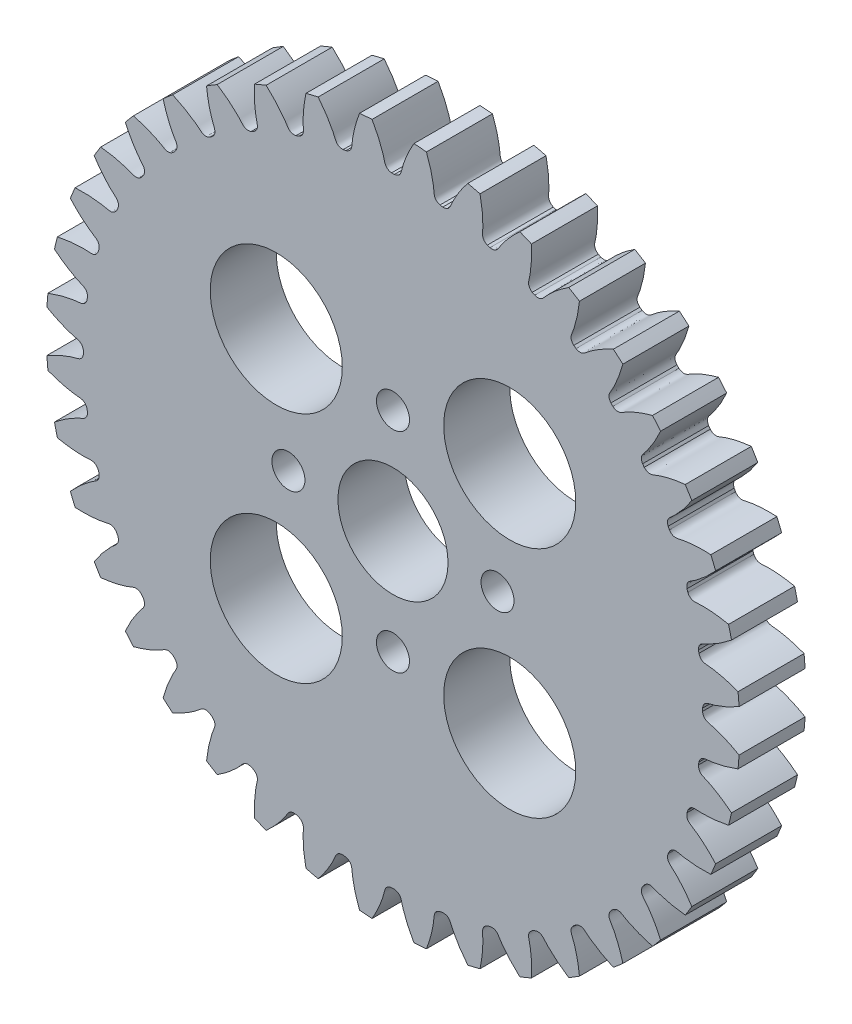
SolidWorks part; units mm, degrees
material "1060 合金"
ref_plane "前视基准面" through (0, 0, 0) normal (0, 0, 1) x (1, 0, 0)
ref_plane "上视基准面" through (0, 0, 0) normal (0, 1, 0) x (1, 0, 0)
ref_plane "右视基准面" through (0, 0, 0) normal (1, 0, 0) x (0, 0, -1)
sketch "草图1" plane through (0, 0, 0) normal (0, 0, 1) x (1, 0, 0)
  circle A0 centre (0, 0) radius 31.5
extrude "凸台-拉伸1" add sketch "草图1" along normal blind 6
ref_axis "基准轴1" through (0, 0, 6) along (0, 0, -1)
sketch "草图2" plane through (0, 0, 0) normal (0, 0, 1) x (1, 0, 0)
  line L0 (0, 0) -> (0, 31.5) construction
  circle A0 centre (0, 0) radius 31.5 construction
  arc A1 (0.1269, 28.1247) -> (-0.1269, 28.1247) centre (0, 0) ccw
  arc A2 (5.5112, 35.817) -> (-5.5112, 35.817) centre (0, 0) ccw
  spline S0 degree 3 poles (0.1269, 28.1247) (0.6835, 28.2061) (0.7342, 28.6057) (0.8505, 29.0343) (0.8909, 29.1739) (0.9376, 29.3234) (0.9908, 29.4826) (1.0509, 29.6514) (1.1184, 29.8294) (1.1937, 30.0166) (1.2771, 30.2125) (1.369, 30.4171) (1.4699, 30.63) (1.58, 30.8509) (1.6997, 31.0795) (1.8294, 31.3156) (1.9694, 31.5588) (2.12, 31.8089) (2.2817, 32.0654) (2.4546, 32.3281) (2.6392, 32.5965) (2.8356, 32.8704) (3.0443, 33.1493) (3.2654, 33.4328) (3.4993, 33.7207) (3.7461, 34.0124) (4.0062, 34.3076) (4.2797, 34.6058) (4.567, 34.9067) (4.9738, 35.3161) (5.2923, 35.6177) (5.5112, 35.817) knots 0 0 0 0 0.110657 0.124739 0.140005 0.156457 0.174093 0.192913 0.212918 0.234108 0.256483 0.280042 0.304786 0.330714 0.357827 0.386125 0.415607 0.446274 0.478126 0.511162 0.545383 0.580789 0.617379 0.655154 0.694113 0.734257 0.775586 0.8181 0.861798 0.906681 1 1 1 1
  spline S1 degree 3 poles (-0.1269, 28.1247) (-0.6835, 28.2061) (-0.7342, 28.6057) (-0.8505, 29.0343) (-0.8909, 29.1739) (-0.9376, 29.3234) (-0.9908, 29.4826) (-1.0509, 29.6514) (-1.1184, 29.8294) (-1.1937, 30.0166) (-1.2771, 30.2125) (-1.369, 30.4171) (-1.4699, 30.63) (-1.58, 30.8509) (-1.6997, 31.0795) (-1.8294, 31.3156) (-1.9694, 31.5588) (-2.12, 31.8089) (-2.2817, 32.0654) (-2.4546, 32.3281) (-2.6392, 32.5965) (-2.8356, 32.8704) (-3.0443, 33.1493) (-3.2654, 33.4328) (-3.4993, 33.7207) (-3.7461, 34.0124) (-4.0062, 34.3076) (-4.2797, 34.6058) (-4.567, 34.9067) (-4.9738, 35.3161) (-5.2923, 35.6177) (-5.5112, 35.817) knots 0 0 0 0 0.110657 0.124739 0.140005 0.156457 0.174093 0.192913 0.212918 0.234108 0.256483 0.280042 0.304786 0.330714 0.357827 0.386125 0.415607 0.446274 0.478126 0.511162 0.545383 0.580789 0.617379 0.655154 0.694113 0.734257 0.775586 0.8181 0.861798 0.906681 1 1 1 1
extrude "切除-拉伸1" cut sketch "草图2" along normal through all
pattern_circular "阵列(圆周)1" count 40 every 9 about axis through (0, 0, 6) along (0, 0, -1) of "切除-拉伸1"
sketch "草图3" plane through (0, 0, 0) normal (0, 0, 1) x (1, 0, 0)
  circle A0 centre (0, 0) radius 30 construction
  dimension "Dn" = 60
sketch "草图4" plane through (0, 0, 6) normal (0, 0, 1) x (1, 0, 0)
  circle A0 centre (0, 0) radius 5
  dimension "D1" = 10
extrude "切除-拉伸2" cut sketch "草图4" against normal blind 10
sketch "草图5" plane through (0, 0, 6) normal (0, 0, 1) x (1, 0, 0)
  circle A0 centre (0, 0) radius 9.5 construction
  circle A1 centre (0, 9.5) radius 1.5
  circle A2 centre (9.5, 0) radius 1.5
  circle A3 centre (0, -9.5) radius 1.5
  circle A4 centre (-9.5, 0) radius 1.5
  point P14 (0, 0)
  dimension "D1" = 19
  dimension "D2" = 3
  dimension "D3" = 4
extrude "切除-拉伸3" cut sketch "草图5" against normal blind 10
sketch "草图6" plane through (0, 0, 6) normal (0, 0, 1) x (1, 0, 0)
  line L0 (15, 0) -> (0, 0) construction
  line L1 (0, 0) -> (10.6066, 10.6066) construction
  circle A0 centre (0, 0) radius 15 construction
  circle A3 centre (10.6066, 10.6066) radius 6
  circle A4 centre (10.6066, -10.6066) radius 6
  circle A5 centre (-10.6066, -10.6066) radius 6
  circle A6 centre (-10.6066, 10.6066) radius 6
  point P15 (0, 0)
  dimension "D1" = 30
  dimension "D3" = 12
  dimension "D4" = 4
  dimension "D2" = 45
extrude "切除-拉伸4" cut sketch "草图6" against normal blind 10
